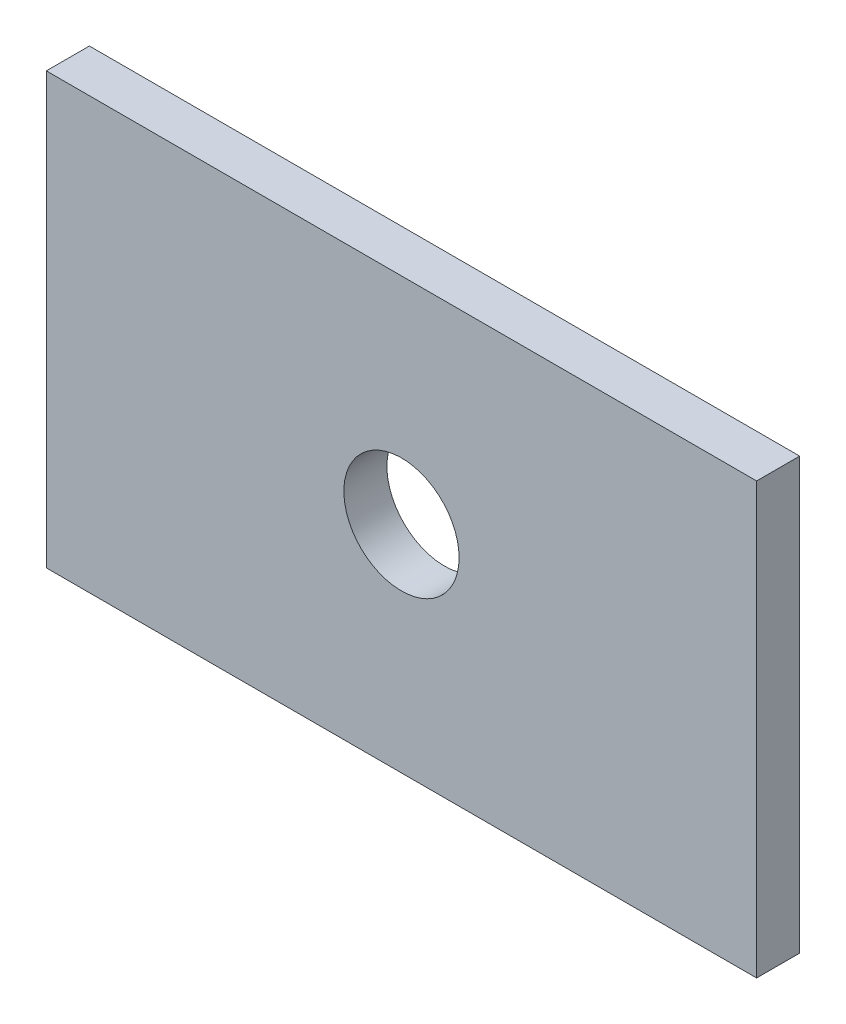
SolidWorks part; units mm, degrees
ref_plane "Front Plane" through (0, 0, 0) normal (0, 0, 1) x (1, 0, 0)
ref_plane "Top Plane" through (0, 0, 0) normal (0, 1, 0) x (1, 0, 0)
ref_plane "Right Plane" through (0, 0, 0) normal (1, 0, 0) x (0, 0, -1)
sketch "Sketch1" plane through (0, 0, 0) normal (0, 0, 1) x (1, 0, 0)
  line L1 (-52.3875, 31.75) -> (52.3875, 31.75)
  line L2 (-52.3875, 31.75) -> (-52.3875, -31.75)
  line L3 (-52.3875, -31.75) -> (52.3875, -31.75)
  line L4 (52.3875, 31.75) -> (52.3875, -31.75)
  line L5 (-52.3875, 31.75) -> (52.3875, -31.75) construction
  line L6 (-52.3875, -31.75) -> (52.3875, 31.75) construction
  point P0 (0, 0)
  dimension "D1" = 63.5
  dimension "D2" = 104.775
extrude "Boss-Extrude1" add sketch "Sketch1" along normal blind 6.35
sketch "Sketch2" plane through (0, 0, 6.35) normal (0, 0, 1) x (1, 0, 0)
  circle A0 centre (0, 0) radius 8.5
extrude "Cut-Extrude1" cut sketch "Sketch2" against normal up to next
